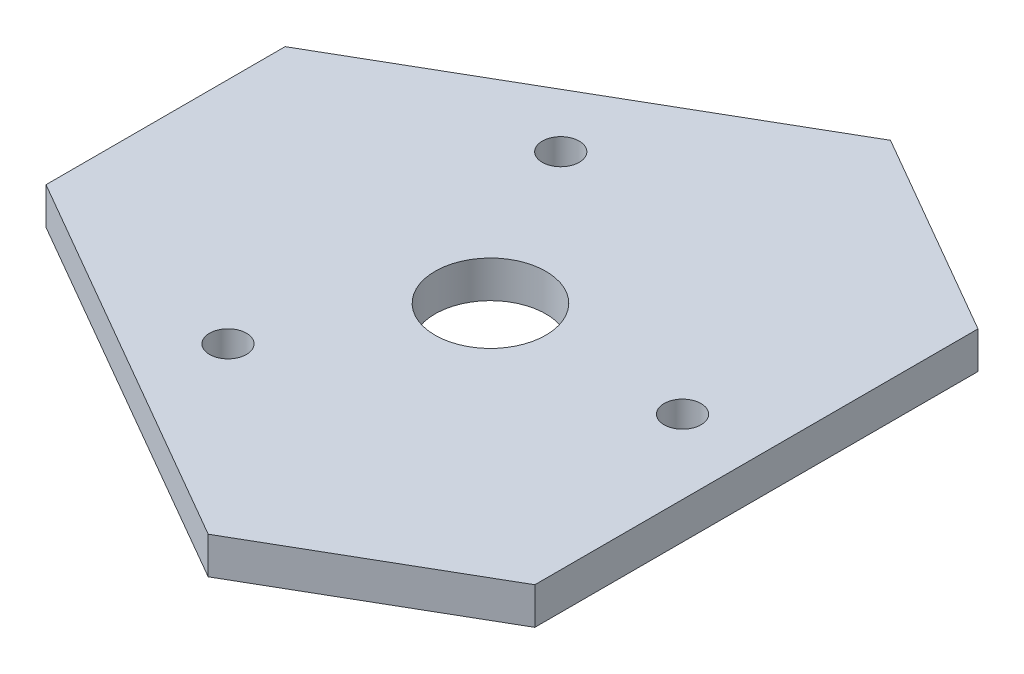
SolidWorks part; units mm, degrees
ref_plane "Front Plane" through (0, 0, 0) normal (0, 0, 1) x (1, 0, 0)
ref_plane "Top Plane" through (0, 0, 0) normal (0, 1, 0) x (1, 0, 0)
ref_plane "Right Plane" through (0, 0, 0) normal (1, 0, 0) x (0, 0, -1)
sketch "Sketch2" plane through (0, 0, 0) normal (0, 1, 0) x (1, 0, 0)
  line L0 (0, 0) -> (-43656.8426, 0) construction
  line L1 (22.8681, 19.05) -> (22.8681, -19.05)
  line L2 (22.8681, 39.6088) -> (-45.7363, 0) construction
  line L3 (-45.7363, 0) -> (22.8681, -39.6088) construction
  line L4 (22.8681, -39.6088) -> (22.8681, 39.6088) construction
  line L5 (22.8681, -19.05) -> (5.0637, -29.3294)
  line L6 (5.0637, -29.3294) -> (-27.9319, -10.2794)
  line L7 (-0.0355, 0.0615) -> (21828.3858, -37807.8732) construction
  line L8 (40.0162, 69.3101) -> (-21788.4051, -37738.6247) construction
  line L9 (-27.9319, -10.2794) -> (-27.9319, 10.2794)
  line L10 (-27.9319, 10.2794) -> (5.0637, 29.3294)
  line L11 (5.0637, 29.3294) -> (22.8681, 19.05)
  circle A0 centre (0, 0) radius 45.7363 construction
  circle A1 centre (16.5181, 0) radius 1.5875
  circle A2 centre (-8.2591, -14.3051) radius 1.5875
  circle A3 centre (-8.2591, 14.3051) radius 1.5875
  circle A4 centre (0, 0) radius 4.7625
  dimension "D2" = 3.175
  dimension "D3" = 9.525
  dimension "D1" = 38.1
  dimension "D4" = 3
  dimension "D5" = 6.35
  dimension "D6" = 50.8
extrude "Boss-Extrude2" add sketch "Sketch2" along normal blind 3.175
